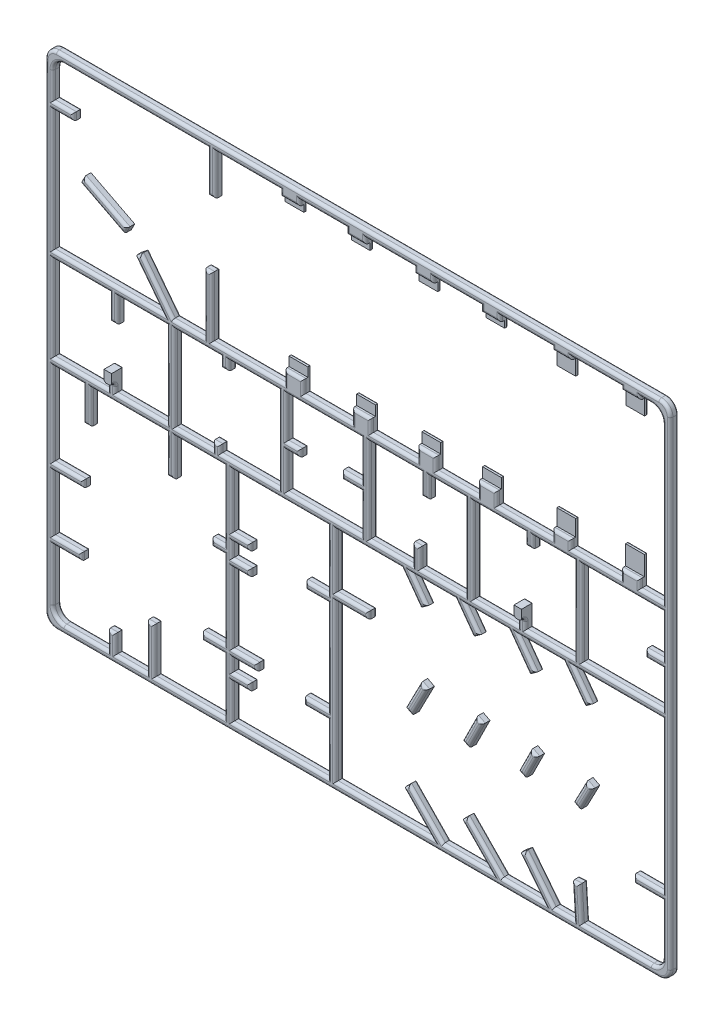
SolidWorks part; units mm, degrees
ref_plane "Front" through (0, 0, 0) normal (0, 0, 1) x (1, 0, 0)
ref_plane "Top" through (0, 0, 0) normal (0, 1, 0) x (1, 0, 0)
ref_plane "Right" through (0, 0, 0) normal (1, 0, 0) x (0, 0, -1)
sketch "Sketch1" plane through (0, 0, 0) normal (0, 0, 1) x (1, 0, 0)
  line L0 (81.8978, -5.241) -> (-82.5193, -5.241)
  line L1 (-34.8288, -65.5735) -> (-34.8288, -5.241)
  line L2 (-82.5193, -65.5735) -> (81.8978, -65.5735)
  line L3 (-82.5193, -65.5735) -> (-82.5193, 65.8623)
  line L4 (-82.5193, 65.8623) -> (81.8978, 65.8623)
  line L5 (81.8978, -65.5735) -> (81.8978, 65.8623)
  line L6 (81.8978, 6.4099) -> (76.3433, 6.4099)
  line L7 (81.8978, 19.4574) -> (-82.5193, 19.4574)
  line L8 (-20.3529, -5.241) -> (-20.3529, 19.4574)
  line L9 (29.3632, -5.241) -> (29.3632, 19.4574)
  line L10 (1.6703, -5.241) -> (1.6703, 19.4574)
  line L11 (-65.8761, -59.6507) -> (-65.8761, -65.5735)
  line L12 (-73.815, -46.4581) -> (-82.5193, -46.4581)
  line L13 (-73.2731, -29.4196) -> (-82.5193, -29.4196)
  line L14 (-72.4385, -15.3166) -> (-72.4385, -5.241)
  line L15 (-41.8719, -48.6764) -> (-34.8288, -48.6764)
  line L16 (-39.2627, -25.7118) -> (-34.8288, -25.7118)
  line L17 (-50.1045, -16.3197) -> (-50.1045, -5.241)
  line L18 (-55.508, -52.42) -> (-55.508, -65.5735)
  line L19 (58.3675, -5.241) -> (58.3675, 19.4574)
  line L20 (-28.9413, -27.8132) -> (-34.8288, -27.8132)
  line L22 (-50.1045, -5.241) -> (-50.1045, 19.4574)
  line L23 (-28.9413, -54.1411) -> (-34.8288, -54.1411)
  line L24 (58.3675, 11.7403) -> (64.5416, 11.7403)
  line L26 (73.1723, -47.1731) -> (81.8978, -47.1731)
  line L27 (-7.2383, -65.5735) -> (-7.2383, -5.241)
  line L28 (-14.2565, -23.1079) -> (-7.2383, -23.1079)
  line L29 (2.5177, -21.8865) -> (-7.2383, -21.8865)
  line L30 (17.225, -12.5359) -> (11.9277, -5.241)
  line L31 (31.253, -12.2024) -> (26.1979, -5.241)
  line L32 (46.253, -13.3582) -> (40.3586, -5.241)
  line L33 (60.9589, -13.3582) -> (55.0137, -5.241)
  line L35 (57.7443, -55.7789) -> (58.3675, -65.5735)
  line L36 (43.6229, -55.7789) -> (51.3233, -65.5735)
  line L37 (28.0749, -55.7789) -> (37.6274, -65.5735)
  line L38 (12.6161, -56.0751) -> (21.8796, -65.5735)
  line L39 (43.3628, -38.0091) -> (46.5638, -31.5955)
  line L40 (57.9117, -38.0091) -> (61.2697, -31.5955)
  line L41 (28.3857, -38.5772) -> (32.0401, -31.2551)
  line L42 (13.1916, -38.5772) -> (17.225, -30.7859)
  line L43 (53.9902, 19.4574) -> (53.9902, 27.0124)
  line L44 (-65.3524, 11.7403) -> (-65.3524, 19.4574)
  line L45 (72.2906, 27.8612) -> (72.2906, 19.4574)
  line L46 (72.3535, 59.8242) -> (72.3535, 65.8623)
  line L47 (53.9902, 59.8242) -> (53.9902, 65.8623)
  line L48 (35.049, 61.4294) -> (35.049, 65.8623)
  line L49 (34.1875, 26.5614) -> (34.1875, 19.4574)
  line L50 (18.0557, 26.5614) -> (18.0557, 19.4574)
  line L51 (0.6748, 26.5614) -> (0.6748, 19.4574)
  line L52 (-17.3279, 26.3151) -> (-17.3279, 19.4574)
  line L53 (-18.3945, 61.4294) -> (-18.3945, 65.8623)
  line L54 (-0.7731, 61.4294) -> (-0.7731, 65.8623)
  line L55 (17.2678, 60.9572) -> (17.2678, 65.8623)
  line L56 (-39.2627, 53.8546) -> (-39.2627, 65.8623)
  line L57 (-40.1658, 36.4171) -> (-40.1658, 19.4574)
  line L58 (-58.8285, 30.7449) -> (-50.1045, 19.4574)
  line L59 (-73.815, 40.5918) -> (-62.1369, 34.5937)
  line L60 (-82.5193, 53.8546) -> (-75.9828, 53.8546)
  line L61 (17.5915, 12.8902) -> (17.5915, 19.4574)
  line L62 (43.3059, 1.1119) -> (43.3059, -5.241)
  line L63 (-37.9496, -2.2) -> (-37.9496, -5.241)
  line L65 (-14.6056, -50.053) -> (-7.2383, -50.053)
  line L66 (28.419, -16.2498) -> (32.3184, -10.6808) construction
  line L67 (-65.8761, -5.241) -> (-65.8761, 0.8715)
  line L68 (-35.7693, 19.4574) -> (-35.7693, 15.7952)
  line L69 (-20.3529, 6.4099) -> (-15.6719, 6.4099)
  line L70 (15.2912, 0.8715) -> (15.2912, -5.241)
  line L71 (45.3566, 15.3416) -> (45.3566, 19.4574)
  line L72 (1.6703, 7.1082) -> (-4.567, 7.1082)
  line L73 (-34.8288, -48.6764) -> (-27.1043, -48.6764)
  line L74 (-34.8288, -21.8865) -> (-28.9413, -21.8865)
  point P122 (-55.508, -52.42)
  point P130 (-39.2627, -25.7118)
  point P131 (-65.3524, 11.7403)
sketch "Sketch3" plane through (0, 0, 0) normal (0, 0, 1) x (1, 0, 0)
  line L0 (1.6703, -5.241) -> (1.6703, 19.4574) construction
  line L1 (29.3632, -5.241) -> (29.3632, 19.4574) construction
  line L2 (-20.3529, -5.241) -> (-20.3529, 19.4574) construction
  line L3 (81.8978, 19.4574) -> (-82.5193, 19.4574) construction
  line L4 (-82.5193, -65.5735) -> (81.8978, -65.5735)
  line L5 (81.8978, -65.5735) -> (81.8978, 65.8623)
  line L6 (81.8978, 65.8623) -> (-82.5193, 65.8623)
  line L7 (-82.5193, 65.8623) -> (-82.5193, -65.5735)
  line L8 (-82.5193, -65.5735) -> (81.8978, -65.5735) construction
  line L9 (81.8978, -65.5735) -> (81.8978, 65.8623) construction
  line L10 (81.8978, 65.8623) -> (-82.5193, 65.8623) construction
  line L11 (-82.5193, 65.8623) -> (-82.5193, -65.5735) construction
  line L12 (-34.8288, -65.5735) -> (-34.8288, -5.241) construction
  line L13 (81.8978, -5.241) -> (-82.5193, -5.241) construction
  line L14 (-55.508, -52.42) -> (-55.508, -65.5735) construction
  line L15 (-50.1045, -16.3197) -> (-50.1045, -5.241) construction
  line L16 (-50.1045, -5.241) -> (-50.1045, 19.4574) construction
  line L17 (-58.8285, 30.7449) -> (-50.1045, 19.4574) construction
  line L18 (-39.2627, -25.7118) -> (-34.8288, -25.7118) construction
  line L19 (-41.8719, -48.6764) -> (-34.8288, -48.6764) construction
  line L20 (-72.4385, -15.3166) -> (-72.4385, -5.241) construction
  line L21 (-73.2731, -29.4196) -> (-82.5193, -29.4196) construction
  line L22 (-73.815, -46.4581) -> (-82.5193, -46.4581) construction
  line L23 (-65.8761, -59.6507) -> (-65.8761, -65.5735) construction
  line L24 (53.9902, 19.4574) -> (53.9902, 27.0124) construction
  line L25 (73.1723, -47.1731) -> (81.8978, -47.1731) construction
  line L27 (58.3675, 11.7403) -> (64.5416, 11.7403) construction
  line L28 (-28.9413, -54.1411) -> (-34.8288, -54.1411) construction
  line L29 (44.3566, 15.3416) -> (46.3566, 15.3416)
  line L30 (-28.9413, -27.8132) -> (-34.8288, -27.8132) construction
  line L31 (58.3675, -5.241) -> (58.3675, 19.4574) construction
  line L32 (46.3566, 15.3416) -> (46.3566, 19.4574)
  line L33 (60.9589, -13.3582) -> (55.0137, -5.241) construction
  line L34 (46.253, -13.3582) -> (40.3586, -5.241) construction
  line L35 (31.253, -12.2024) -> (26.1979, -5.241) construction
  line L36 (17.225, -12.5359) -> (11.9277, -5.241) construction
  line L37 (2.5177, -21.8865) -> (-7.2383, -21.8865) construction
  line L38 (-14.2565, -23.1079) -> (-7.2383, -23.1079) construction
  line L39 (-7.2383, -65.5735) -> (-7.2383, -5.241) construction
  line L40 (13.1916, -38.5772) -> (17.225, -30.7859) construction
  line L41 (28.3857, -38.5772) -> (32.0401, -31.2551) construction
  line L42 (57.9117, -38.0091) -> (61.2697, -31.5955) construction
  line L43 (43.3628, -38.0091) -> (46.5638, -31.5955) construction
  line L44 (12.6161, -56.0751) -> (21.8796, -65.5735) construction
  line L45 (28.0749, -55.7789) -> (37.6274, -65.5735) construction
  line L46 (43.6229, -55.7789) -> (51.3233, -65.5735) construction
  line L47 (57.7443, -55.7789) -> (58.3675, -65.5735) construction
  line L48 (18.0557, 26.5614) -> (18.0557, 19.4574) construction
  line L49 (34.1875, 26.5614) -> (34.1875, 19.4574) construction
  line L50 (35.049, 61.4294) -> (35.049, 65.8623) construction
  line L51 (53.9902, 59.8242) -> (53.9902, 65.8623) construction
  line L52 (72.3535, 59.8242) -> (72.3535, 65.8623) construction
  line L53 (72.2906, 27.8612) -> (72.2906, 19.4574) construction
  line L54 (-65.3524, 11.7403) -> (-65.3524, 19.4574) construction
  line L55 (81.8978, 6.4099) -> (76.3433, 6.4099) construction
  line L56 (-40.1658, 36.4171) -> (-40.1658, 19.4574) construction
  line L57 (-39.2627, 53.8546) -> (-39.2627, 65.8623) construction
  line L58 (17.2678, 60.9572) -> (17.2678, 65.8623) construction
  line L59 (-0.7731, 61.4294) -> (-0.7731, 65.8623) construction
  line L60 (-18.3945, 61.4294) -> (-18.3945, 65.8623) construction
  line L61 (-17.3279, 26.3151) -> (-17.3279, 19.4574) construction
  line L62 (0.6748, 26.5614) -> (0.6748, 19.4574) construction
  line L63 (-14.6056, -50.053) -> (-7.2383, -50.053) construction
  line L64 (46.3566, 15.3416) -> (46.3566, 18.4574)
  line L65 (-37.9496, -2.2) -> (-37.9496, -5.241) construction
  line L66 (43.3059, 1.1119) -> (43.3059, -5.241) construction
  line L67 (17.5915, 12.8902) -> (17.5915, 19.4574) construction
  line L68 (-82.5193, 53.8546) -> (-75.9828, 53.8546) construction
  line L69 (-73.815, 40.5918) -> (-62.1369, 34.5937) construction
  line L70 (1.6703, -5.241) -> (1.6703, 19.4574) construction
  line L71 (29.3632, -5.241) -> (29.3632, 19.4574) construction
  line L72 (-20.3529, -5.241) -> (-20.3529, 19.4574) construction
  line L73 (81.8978, 19.4574) -> (-82.5193, 19.4574) construction
  line L74 (-34.8288, -65.5735) -> (-34.8288, -5.241) construction
  line L75 (81.8978, -5.241) -> (-82.5193, -5.241) construction
  line L76 (-55.508, -52.42) -> (-55.508, -65.5735) construction
  line L77 (-50.1045, -16.3197) -> (-50.1045, -5.241) construction
  line L78 (-50.1045, -5.241) -> (-50.1045, 19.4574) construction
  line L79 (-58.8285, 30.7449) -> (-50.1045, 19.4574) construction
  line L80 (-39.2627, -25.7118) -> (-34.8288, -25.7118) construction
  line L81 (-41.8719, -48.6764) -> (-34.8288, -48.6764) construction
  line L82 (-72.4385, -15.3166) -> (-72.4385, -5.241) construction
  line L83 (-73.2731, -29.4196) -> (-82.5193, -29.4196) construction
  line L84 (-73.815, -46.4581) -> (-82.5193, -46.4581) construction
  line L85 (-65.8761, -59.6507) -> (-65.8761, -65.5735) construction
  line L86 (53.9902, 19.4574) -> (53.9902, 27.0124) construction
  line L87 (73.1723, -47.1731) -> (81.8978, -47.1731) construction
  line L88 (44.3566, 15.3416) -> (44.3566, 19.4574)
  line L89 (58.3675, 11.7403) -> (64.5416, 11.7403) construction
  line L90 (-28.9413, -54.1411) -> (-34.8288, -54.1411) construction
  line L91 (44.3566, 15.3416) -> (44.3566, 18.4574)
  line L92 (-28.9413, -27.8132) -> (-34.8288, -27.8132) construction
  line L93 (58.3675, -5.241) -> (58.3675, 19.4574) construction
  line L94 (-36.7693, 15.7952) -> (-34.7693, 15.7952)
  line L95 (60.9589, -13.3582) -> (55.0137, -5.241) construction
  line L96 (46.253, -13.3582) -> (40.3586, -5.241) construction
  line L97 (31.253, -12.2024) -> (26.1979, -5.241) construction
  line L98 (17.225, -12.5359) -> (11.9277, -5.241) construction
  line L99 (2.5177, -21.8865) -> (-7.2383, -21.8865) construction
  line L100 (-14.2565, -23.1079) -> (-7.2383, -23.1079) construction
  line L101 (-7.2383, -65.5735) -> (-7.2383, -5.241) construction
  line L102 (13.1916, -38.5772) -> (17.225, -30.7859) construction
  line L103 (28.3857, -38.5772) -> (32.0401, -31.2551) construction
  line L104 (57.9117, -38.0091) -> (61.2697, -31.5955) construction
  line L105 (43.3628, -38.0091) -> (46.5638, -31.5955) construction
  line L106 (12.6161, -56.0751) -> (21.8796, -65.5735) construction
  line L107 (28.0749, -55.7789) -> (37.6274, -65.5735) construction
  line L108 (43.6229, -55.7789) -> (51.3233, -65.5735) construction
  line L109 (57.7443, -55.7789) -> (58.3675, -65.5735) construction
  line L110 (18.0557, 26.5614) -> (18.0557, 19.4574) construction
  line L111 (34.1875, 26.5614) -> (34.1875, 19.4574) construction
  line L112 (35.049, 61.4294) -> (35.049, 65.8623) construction
  line L113 (53.9902, 59.8242) -> (53.9902, 65.8623) construction
  line L114 (72.3535, 59.8242) -> (72.3535, 65.8623) construction
  line L115 (72.2906, 27.8612) -> (72.2906, 19.4574) construction
  line L116 (-65.3524, 11.7403) -> (-65.3524, 19.4574) construction
  line L117 (81.8978, 6.4099) -> (76.3433, 6.4099) construction
  line L118 (-40.1658, 36.4171) -> (-40.1658, 19.4574) construction
  line L119 (-39.2627, 53.8546) -> (-39.2627, 65.8623) construction
  line L120 (17.2678, 60.9572) -> (17.2678, 65.8623) construction
  line L121 (-0.7731, 61.4294) -> (-0.7731, 65.8623) construction
  line L122 (-18.3945, 61.4294) -> (-18.3945, 65.8623) construction
  line L123 (-17.3279, 26.3151) -> (-17.3279, 19.4574) construction
  line L124 (0.6748, 26.5614) -> (0.6748, 19.4574) construction
  line L125 (-14.6056, -50.053) -> (-7.2383, -50.053) construction
  line L126 (44.3566, 18.4574) -> (30.3632, 18.4574)
  line L127 (-37.9496, -2.2) -> (-37.9496, -5.241) construction
  line L128 (43.3059, 1.1119) -> (43.3059, -5.241) construction
  line L129 (17.5915, 12.8902) -> (17.5915, 19.4574) construction
  line L130 (-82.5193, 53.8546) -> (-75.9828, 53.8546) construction
  line L131 (-73.815, 40.5918) -> (-62.1369, 34.5937) construction
  line L132 (-80.5193, -66.5735) -> (79.8978, -66.5735)
  line L133 (82.8978, -63.5735) -> (82.8978, 63.8623)
  line L134 (79.8978, 66.8623) -> (-80.5193, 66.8623)
  line L135 (-83.5193, 63.8623) -> (-83.5193, -63.5735)
  line L136 (2.6703, -4.241) -> (2.6703, 18.4574)
  line L137 (30.3632, -4.241) -> (30.3632, 18.4574)
  line L138 (-19.3529, -4.241) -> (-19.3529, 5.4099)
  line L139 (80.8978, 20.4574) -> (74.7906, 20.4574)
  line L140 (-33.8288, -64.5735) -> (-33.8288, -55.1411)
  line L141 (80.8978, -4.241) -> (59.3675, -4.241)
  line L142 (-56.508, -52.42) -> (-56.508, -64.5735)
  line L143 (-49.1045, -16.3197) -> (-49.1045, -6.241)
  line L144 (-49.1045, -4.241) -> (-49.1045, 18.4574)
  line L145 (-58.0373, 31.3564) -> (-49.6135, 20.4574)
  line L146 (-39.2627, -26.7118) -> (-35.8288, -26.7118)
  line L147 (-41.8719, -49.6764) -> (-35.8288, -49.6764)
  line L148 (-71.4385, -15.3166) -> (-71.4385, -6.241)
  line L149 (-73.2731, -28.4196) -> (-81.5193, -28.4196)
  line L150 (-73.815, -45.4581) -> (-81.5193, -45.4581)
  line L151 (-66.8761, -59.6507) -> (-66.8761, -64.5735)
  line L152 (56.4902, 20.4574) -> (56.4902, 27.0124)
  line L153 (73.1723, -48.1731) -> (80.8978, -48.1731)
  line L155 (59.3675, 10.7403) -> (64.5416, 10.7403)
  line L156 (-28.9413, -53.1411) -> (-33.8288, -53.1411)
  line L158 (-28.9413, -26.8132) -> (-33.8288, -26.8132)
  line L159 (59.3675, -4.241) -> (59.3675, 10.7403)
  line L161 (61.7657, -12.7673) -> (56.9857, -6.241)
  line L162 (47.0622, -12.7706) -> (42.3207, -6.241)
  line L163 (32.0622, -11.6148) -> (28.1599, -6.241)
  line L164 (18.0342, -11.9484) -> (13.8897, -6.241)
  line L165 (2.5177, -20.8865) -> (-6.2383, -20.8865)
  line L166 (-14.2565, -24.1079) -> (-8.2383, -24.1079)
  line L167 (-6.2383, -64.5735) -> (-6.2383, -22.8865)
  line L168 (14.0797, -39.0369) -> (18.1131, -31.2457)
  line L169 (29.2805, -39.0237) -> (32.9349, -31.7017)
  line L170 (58.7976, -38.473) -> (62.1556, -32.0593)
  line L171 (44.2575, -38.4557) -> (47.4585, -32.042)
  line L172 (11.9002, -56.7733) -> (19.5075, -64.5735)
  line L173 (27.359, -56.4771) -> (35.2553, -64.5735)
  line L174 (42.8368, -56.3969) -> (49.265, -64.5735)
  line L175 (56.7464, -55.8424) -> (57.3019, -64.5735)
  line L176 (15.5557, 26.5614) -> (15.5557, 20.4574)
  line L177 (31.6875, 26.5614) -> (31.6875, 20.4574)
  line L178 (37.549, 61.4294) -> (37.549, 64.8623)
  line L179 (56.4902, 59.8242) -> (56.4902, 64.8623)
  line L180 (74.8535, 59.8242) -> (74.8535, 64.8623)
  line L181 (69.7906, 27.8612) -> (69.7906, 20.4574)
  line L182 (-64.3524, 11.7403) -> (-64.3524, 18.4574)
  line L183 (80.8978, 7.4099) -> (76.3433, 7.4099)
  line L184 (-41.1658, 36.4171) -> (-41.1658, 20.4574)
  line L185 (-38.2627, 53.8546) -> (-38.2627, 64.8623)
  line L186 (19.7678, 60.9572) -> (19.7678, 64.8623)
  line L187 (1.7269, 61.4294) -> (1.7269, 64.8623)
  line L188 (-15.8945, 61.4294) -> (-15.8945, 64.8623)
  line L189 (-19.8279, 26.3151) -> (-19.8279, 20.4574)
  line L190 (-1.8252, 26.5614) -> (-1.8252, 20.4574)
  line L191 (-14.6056, -51.053) -> (-8.2383, -51.053)
  line L193 (-38.9496, -2.2) -> (-38.9496, -4.241)
  line L194 (42.3059, 1.1119) -> (42.3059, -4.241)
  line L195 (18.5915, 12.8902) -> (18.5915, 18.4574)
  line L196 (-81.5193, 52.8546) -> (-75.9828, 52.8546)
  line L197 (-74.2719, 39.7022) -> (-62.5938, 33.7042)
  line L198 (-78.5193, -64.5735) -> (-66.8761, -64.5735)
  line L199 (80.8978, -61.5735) -> (80.8978, -48.1731)
  line L200 (77.8978, 64.8623) -> (74.8535, 64.8623)
  line L201 (-81.5193, 61.8623) -> (-81.5193, 54.8546)
  line L202 (0.6703, -4.241) -> (0.6703, 6.1082)
  line L203 (28.3632, -4.241) -> (28.3632, 18.4574)
  line L204 (-21.3529, -4.241) -> (-21.3529, 18.4574)
  line L205 (80.8978, 18.4574) -> (59.3675, 18.4574)
  line L206 (-35.8288, -64.5735) -> (-35.8288, -49.6764)
  line L207 (80.8978, -6.241) -> (56.9857, -6.241)
  line L208 (-54.508, -52.42) -> (-54.508, -64.5735)
  line L209 (-51.1045, -16.3197) -> (-51.1045, -6.241)
  line L210 (-51.1045, -4.241) -> (-51.1045, 18.4574)
  line L211 (-59.6197, 30.1333) -> (-52.1413, 20.4574)
  line L212 (-39.2627, -24.7118) -> (-35.8288, -24.7118)
  line L213 (-41.8719, -47.6764) -> (-35.8288, -47.6764)
  line L214 (-73.4385, -15.3166) -> (-73.4385, -6.241)
  line L215 (-73.2731, -30.4196) -> (-81.5193, -30.4196)
  line L216 (-73.815, -47.4581) -> (-81.5193, -47.4581)
  line L217 (-64.8761, -59.6507) -> (-64.8761, -64.5735)
  line L218 (51.4902, 20.4574) -> (51.4902, 27.0124)
  line L219 (73.1723, -46.1731) -> (80.8978, -46.1731)
  line L221 (59.3675, 7.9351) -> (64.5416, 7.9351)
  line L222 (-28.9413, -55.1411) -> (-33.8288, -55.1411)
  line L224 (-28.9413, -28.8132) -> (-33.8288, -28.8132)
  line L225 (57.3675, -4.241) -> (57.3675, 18.4574)
  line L227 (60.1522, -13.949) -> (54.5066, -6.241)
  line L228 (45.4439, -13.9457) -> (39.849, -6.241)
  line L229 (30.4438, -12.79) -> (25.6882, -6.241)
  line L230 (16.4159, -13.1235) -> (11.418, -6.241)
  line L231 (2.5177, -22.8865) -> (-6.2383, -22.8865)
  line L232 (-14.2565, -22.1079) -> (-8.2383, -22.1079)
  line L233 (-8.2383, -64.5735) -> (-8.2383, -51.053)
  line L234 (12.3035, -38.1174) -> (16.337, -30.3262)
  line L235 (27.491, -38.1306) -> (31.1454, -30.8085)
  line L236 (57.0258, -37.5453) -> (60.3838, -31.1316)
  line L237 (42.468, -37.5626) -> (45.669, -31.1489)
  line L238 (13.332, -55.3769) -> (22.3011, -64.5735)
  line L239 (28.7909, -55.0807) -> (38.0489, -64.5735)
  line L240 (44.4091, -55.1608) -> (51.8091, -64.5735)
  line L241 (58.7423, -55.7154) -> (59.3059, -64.5735)
  line L242 (20.5557, 26.5614) -> (20.5557, 20.4574)
  line L243 (36.6875, 26.5614) -> (36.6875, 20.4574)
  line L244 (32.549, 61.4294) -> (32.549, 64.8623)
  line L245 (51.4902, 59.8242) -> (51.4902, 64.8623)
  line L246 (69.8535, 59.8242) -> (69.8535, 64.8623)
  line L247 (74.7906, 27.8612) -> (74.7906, 20.4574)
  line L248 (-66.3524, 11.7403) -> (-66.3524, 18.4574)
  line L249 (80.8978, 5.4099) -> (76.3433, 5.4099)
  line L250 (-39.1658, 36.4171) -> (-39.1658, 20.4574)
  line L251 (-40.2627, 53.8546) -> (-40.2627, 64.8623)
  line L252 (14.7678, 60.9572) -> (14.7678, 64.8623)
  line L253 (-3.2731, 61.4294) -> (-3.2731, 64.8623)
  line L254 (-20.8945, 61.4294) -> (-20.8945, 64.8623)
  line L255 (-14.8279, 26.3151) -> (-14.8279, 20.4574)
  line L256 (3.1748, 26.5614) -> (3.1748, 20.4574)
  line L257 (-14.6056, -49.053) -> (-8.2383, -49.053)
  line L259 (-36.9496, -2.2) -> (-36.9496, -4.241)
  line L260 (44.3059, 1.1119) -> (44.3059, -4.241)
  line L261 (16.5915, 12.8902) -> (16.5915, 18.4574)
  line L262 (-81.5193, 54.8546) -> (-75.9828, 54.8546)
  line L263 (-73.3581, 41.4813) -> (-61.6801, 35.4832)
  line L264 (-59.6197, 30.1333) -> (-58.0373, 31.3564)
  line L265 (-41.1658, 36.4171) -> (-39.1658, 36.4171)
  line L266 (-19.8279, 26.3151) -> (-14.8279, 26.3151)
  line L267 (-1.8252, 26.5614) -> (3.1748, 26.5614)
  line L268 (15.5557, 26.5614) -> (20.5557, 26.5614)
  line L269 (31.6875, 26.5614) -> (36.6875, 26.5614)
  line L270 (51.4902, 27.0124) -> (56.4902, 27.0124)
  line L271 (76.3433, 5.4099) -> (76.3433, 7.4099)
  line L272 (64.5416, 7.9351) -> (64.5416, 10.7403)
  line L273 (69.7906, 27.8612) -> (74.7906, 27.8612)
  line L274 (74.8535, 59.8242) -> (69.8535, 59.8242)
  line L275 (51.4902, 59.8242) -> (56.4902, 59.8242)
  line L276 (14.7678, 60.9572) -> (19.7678, 60.9572)
  line L277 (32.549, 61.4294) -> (37.549, 61.4294)
  line L278 (-3.2731, 61.4294) -> (1.7269, 61.4294)
  line L279 (-20.8945, 61.4294) -> (-15.8945, 61.4294)
  line L280 (-62.5938, 33.7042) -> (-61.6801, 35.4832)
  line L281 (-73.3581, 41.4813) -> (-74.2719, 39.7022)
  line L282 (-75.9828, 52.8546) -> (-75.9828, 54.8546)
  line L283 (-40.2627, 53.8546) -> (-38.2627, 53.8546)
  line L284 (-66.3524, 11.7403) -> (-64.3524, 11.7403)
  line L285 (-73.4385, -15.3166) -> (-71.4385, -15.3166)
  line L286 (-51.1045, -16.3197) -> (-49.1045, -16.3197)
  line L287 (-39.2627, -24.7118) -> (-39.2627, -26.7118)
  line L288 (-14.2565, -22.1079) -> (-14.2565, -24.1079)
  line L290 (-28.9413, -26.8132) -> (-28.9413, -28.8132)
  line L291 (-73.2731, -28.4196) -> (-73.2731, -30.4196)
  line L293 (2.5177, -22.8865) -> (2.5177, -20.8865)
  line L294 (16.4159, -13.1235) -> (18.0342, -11.9484)
  line L295 (30.4438, -12.79) -> (32.0622, -11.6148)
  line L296 (45.4439, -13.9457) -> (47.0622, -12.7706)
  line L297 (60.1522, -13.949) -> (61.7657, -12.7673)
  line L299 (58.7976, -38.473) -> (57.0258, -37.5453)
  line L300 (45.669, -31.1489) -> (47.4585, -32.042)
  line L301 (60.3838, -31.1316) -> (62.1556, -32.0593)
  line L302 (42.468, -37.5626) -> (44.2575, -38.4557)
  line L303 (27.491, -38.1306) -> (29.2805, -39.0237)
  line L304 (16.337, -30.3262) -> (18.1131, -31.2457)
  line L305 (31.1454, -30.8085) -> (32.9349, -31.7017)
  line L306 (12.3035, -38.1174) -> (14.0797, -39.0369)
  line L307 (73.1723, -46.1731) -> (73.1723, -48.1731)
  line L309 (58.7423, -55.7154) -> (56.7464, -55.8424)
  line L310 (44.4091, -55.1608) -> (42.8368, -56.3969)
  line L311 (28.7909, -55.0807) -> (27.359, -56.4771)
  line L312 (11.9002, -56.7733) -> (13.332, -55.3769)
  line L313 (-28.9413, -53.1411) -> (-28.9413, -55.1411)
  line L314 (-14.6056, -49.053) -> (-14.6056, -51.053)
  line L315 (-41.8719, -47.6764) -> (-41.8719, -49.6764)
  line L316 (-56.508, -52.42) -> (-54.508, -52.42)
  line L317 (16.5915, 12.8902) -> (18.5915, 12.8902)
  line L327 (80.8978, 20.4574) -> (80.8978, 61.8623)
  line L331 (69.7906, 20.4574) -> (56.4902, 20.4574)
  line L333 (57.3675, 18.4574) -> (46.3566, 18.4574)
  line L336 (51.4902, 20.4574) -> (36.6875, 20.4574)
  line L339 (31.6875, 20.4574) -> (20.5557, 20.4574)
  line L342 (28.3632, 18.4574) -> (18.5915, 18.4574)
  line L345 (16.5915, 18.4574) -> (2.6703, 18.4574)
  line L347 (15.5557, 20.4574) -> (3.1748, 20.4574)
  line L351 (0.6703, 18.4574) -> (-19.3529, 18.4574)
  line L354 (-1.8252, 20.4574) -> (-14.8279, 20.4574)
  line L357 (-19.8279, 20.4574) -> (-39.1658, 20.4574)
  line L360 (-21.3529, 18.4574) -> (-34.7693, 18.4574)
  line L363 (-41.1658, 20.4574) -> (-49.6135, 20.4574)
  line L365 (-51.1045, -4.241) -> (-64.8761, -4.241)
  line L367 (-51.1045, 18.4574) -> (-64.3524, 18.4574)
  line L371 (-52.1413, 20.4574) -> (-81.5193, 20.4574)
  line L373 (-66.3524, 18.4574) -> (-81.5193, 18.4574)
  line L375 (-81.5193, 18.4574) -> (-81.5193, -4.241)
  line L377 (-81.5193, 52.8546) -> (-81.5193, 20.4574)
  line L380 (-40.2627, 64.8623) -> (-78.5193, 64.8623)
  line L383 (-20.8945, 64.8623) -> (-38.2627, 64.8623)
  line L386 (14.7678, 64.8623) -> (1.7269, 64.8623)
  line L389 (-3.2731, 64.8623) -> (-15.8945, 64.8623)
  line L392 (32.549, 64.8623) -> (19.7678, 64.8623)
  line L395 (69.8535, 64.8623) -> (56.4902, 64.8623)
  line L398 (51.4902, 64.8623) -> (37.549, 64.8623)
  line L400 (-81.5193, -6.241) -> (-81.5193, -28.4196)
  line L404 (-73.4385, -6.241) -> (-81.5193, -6.241)
  line L407 (-51.1045, -6.241) -> (-71.4385, -6.241)
  line L410 (-38.9496, -4.241) -> (-49.1045, -4.241)
  line L413 (-35.8288, -6.241) -> (-49.1045, -6.241)
  line L415 (-28.9413, -20.8865) -> (-28.9413, -22.8865)
  line L417 (-34.8288, -22.8865) -> (-28.9413, -22.8865)
  line L421 (-8.2383, -6.241) -> (-33.8288, -6.241)
  line L422 (-6.2383, -20.8865) -> (-6.2383, -6.241)
  line L424 (-35.8288, -24.7118) -> (-35.8288, -6.241)
  line L427 (-8.2383, -22.1079) -> (-8.2383, -6.241)
  line L430 (28.3632, -4.241) -> (16.2912, -4.241)
  line L432 (25.6882, -6.241) -> (13.8897, -6.241)
  line L434 (11.418, -6.241) -> (-6.2383, -6.241)
  line L436 (57.3675, -4.241) -> (44.3059, -4.241)
  line L439 (39.849, -6.241) -> (28.1599, -6.241)
  line L442 (54.5066, -6.241) -> (42.3207, -6.241)
  line L445 (42.3059, -4.241) -> (30.3632, -4.241)
  line L448 (59.3675, 7.9351) -> (59.3675, 18.4574)
  line L451 (80.8978, 7.4099) -> (80.8978, 18.4574)
  line L453 (80.8978, -4.241) -> (80.8978, 5.4099)
  line L454 (-36.7693, 19.4574) -> (-36.7693, 15.7952)
  line L456 (-36.7693, 18.4574) -> (-36.7693, 15.7952)
  line L458 (80.8978, -46.1731) -> (80.8978, -6.241)
  line L461 (-34.7693, 19.4574) -> (-34.7693, 15.7952)
  line L462 (59.3059, -64.5735) -> (77.8978, -64.5735)
  line L463 (-34.7693, 18.4574) -> (-34.7693, 15.7952)
  line L466 (-6.2383, -64.5735) -> (19.5075, -64.5735)
  line L468 (51.8091, -64.5735) -> (57.3019, -64.5735)
  line L471 (22.3011, -64.5735) -> (35.2553, -64.5735)
  line L474 (38.0489, -64.5735) -> (49.265, -64.5735)
  line L476 (-33.8288, -64.5735) -> (-8.2383, -64.5735)
  line L478 (-54.508, -64.5735) -> (-35.8288, -64.5735)
  line L481 (-64.8761, -64.5735) -> (-56.508, -64.5735)
  line L484 (-81.5193, -47.4581) -> (-81.5193, -61.5735)
  line L487 (-81.5193, -30.4196) -> (-81.5193, -45.4581)
  line L489 (-27.1043, -47.6764) -> (-27.1043, -49.6764)
  line L490 (-8.2383, -49.053) -> (-8.2383, -24.1079)
  line L491 (-34.8288, -49.6764) -> (-27.1043, -49.6764)
  line L496 (-33.8288, -53.1411) -> (-33.8288, -49.6764)
  line L499 (-35.8288, -47.6764) -> (-35.8288, -26.7118)
  line L501 (-66.8761, -59.6507) -> (-64.8761, -59.6507)
  line L502 (-73.815, -45.4581) -> (-73.815, -47.4581)
  line L503 (-38.9496, -2.2) -> (-36.9496, -2.2)
  line L504 (0.6703, -4.241) -> (-19.3529, -4.241)
  line L505 (42.3059, 1.1119) -> (44.3059, 1.1119)
  line L506 (-21.3529, -4.241) -> (-36.9496, -4.241)
  line L508 (-33.8288, -26.8132) -> (-33.8288, -22.8865)
  line L511 (-64.8761, 0.8715) -> (-66.8761, 0.8715)
  line L512 (-64.8761, -5.241) -> (-64.8761, 0.8715)
  line L513 (-64.8761, -4.241) -> (-64.8761, 0.8715)
  line L514 (-66.8761, -5.241) -> (-66.8761, 0.8715)
  line L515 (-66.8761, -4.241) -> (-66.8761, 0.8715)
  line L516 (-66.8761, -4.241) -> (-81.5193, -4.241)
  line L517 (-36.7693, 18.4574) -> (-49.1045, 18.4574)
  line L523 (-20.3529, 5.4099) -> (-15.6719, 5.4099)
  line L524 (-19.3529, 5.4099) -> (-15.6719, 5.4099)
  line L525 (-20.3529, 7.4099) -> (-15.6719, 7.4099)
  line L526 (-19.3529, 7.4099) -> (-15.6719, 7.4099)
  line L527 (-4.567, 6.1082) -> (-4.567, 8.1082)
  line L528 (1.6703, 8.1082) -> (-4.567, 8.1082)
  line L529 (0.6703, 8.1082) -> (-4.567, 8.1082)
  line L530 (1.6703, 6.1082) -> (-4.567, 6.1082)
  line L531 (0.6703, 6.1082) -> (-4.567, 6.1082)
  line L532 (-15.6719, 5.4099) -> (-15.6719, 7.4099)
  line L533 (-19.3529, 7.4099) -> (-19.3529, 18.4574)
  line L534 (0.6703, 8.1082) -> (0.6703, 18.4574)
  line L536 (16.2912, 0.8715) -> (14.2912, 0.8715)
  line L537 (14.2912, 0.8715) -> (14.2912, -5.241)
  line L538 (14.2912, 0.8715) -> (14.2912, -4.241)
  line L539 (16.2912, 0.8715) -> (16.2912, -5.241)
  line L540 (16.2912, 0.8715) -> (16.2912, -4.241)
  line L541 (14.2912, -4.241) -> (2.6703, -4.241)
  line L542 (-33.8288, -49.6764) -> (-27.1043, -49.6764)
  line L543 (-34.8288, -47.6764) -> (-27.1043, -47.6764)
  line L544 (-33.8288, -47.6764) -> (-27.1043, -47.6764)
  line L545 (-33.8288, -47.6764) -> (-33.8288, -28.8132)
  line L546 (-33.8288, -22.8865) -> (-28.9413, -22.8865)
  line L547 (-34.8288, -20.8865) -> (-28.9413, -20.8865)
  line L548 (-33.8288, -20.8865) -> (-28.9413, -20.8865)
  line L550 (-33.8288, -20.8865) -> (-33.8288, -6.241)
  arc A0 (-80.5193, 66.8623) -> (-83.5193, 63.8623) centre (-80.5193, 63.8623) ccw
  arc A1 (-78.5193, 64.8623) -> (-81.5193, 61.8623) centre (-78.5193, 61.8623) ccw
  arc A2 (-80.5193, -66.5735) -> (-83.5193, -63.5735) centre (-80.5193, -63.5735) cw
  arc A3 (-78.5193, -64.5735) -> (-81.5193, -61.5735) centre (-78.5193, -61.5735) cw
  arc A4 (79.8978, -66.5735) -> (82.8978, -63.5735) centre (79.8978, -63.5735) ccw
  arc A5 (82.8978, 63.8623) -> (79.8978, 66.8623) centre (79.8978, 63.8623) ccw
  arc A6 (80.8978, 61.8623) -> (77.8978, 64.8623) centre (77.8978, 61.8623) ccw
  arc A7 (80.8978, -61.5735) -> (77.8978, -64.5735) centre (77.8978, -61.5735) cw
  point P131 (-33.8288, -51.4087)
  point P132 (-38.9496, -3.2205)
  point P133 (72.2906, 27.8612)
  point P134 (53.9902, 27.0124)
  point P135 (34.1875, 26.5614)
  point P136 (20.2946, 26.6853)
  point P137 (-13.8432, 26.3558)
  point P138 (3.9799, 26.7284)
  point P139 (21.8031, 27.0389)
  point P140 (18.0557, 26.5614)
  point P141 (0.6748, 26.5614)
  point P143 (-17.3279, 26.3151)
  point P145 (0, 0)
  point P146 (-65.3524, 11.7403)
  point P149 (-18.3945, 61.4294)
  point P151 (-0.7731, 61.4294)
  point P153 (17.2678, 60.9572)
  point P155 (35.049, 61.4294)
  point P157 (53.9902, 59.8242)
  point P159 (72.3535, 59.8242)
  dimension "D4" = 3
  dimension "D5" = 3
  dimension "D6" = 1
  dimension "D8" = 1
  dimension "D10" = 1
  dimension "D14" = 1
  dimension "D16" = 1
  dimension "D18" = 1
  dimension "D20" = 1
  dimension "D2" = 1
  dimension "D3" = 1
  dimension "D21" = 1
  dimension "D22" = 1
  dimension "D23" = 1
  dimension "D24" = 1
  dimension "D25" = 1
  dimension "D26" = 1
  dimension "D27" = 1
  dimension "D30" = 1
  dimension "D31" = 1
  dimension "D32" = 1
  dimension "D33" = 1
  dimension "D34" = 1
  dimension "D35" = 1
  dimension "D36" = 1
  dimension "D37" = 1
  dimension "D38" = 1
  dimension "D39" = 1
  dimension "D40" = 1
  dimension "D41" = 1
  dimension "D42" = 1
  dimension "D43" = 1
  dimension "D44" = 1
  dimension "D45" = 1
  dimension "D46" = 1
  dimension "D47" = 1
  dimension "D48" = 1
  dimension "D49" = 1
  dimension "D50" = 1
  dimension "D51" = 1
  dimension "D52" = 1
  dimension "D53" = 1
  dimension "D54" = 1
  dimension "D55" = 1
  dimension "D56" = 1
  dimension "D57" = 1
  dimension "D58" = 2
  dimension "D59" = 1
  dimension "D60" = 1
  dimension "D61" = 1
  dimension "D62" = 1
  dimension "D63" = 1
  dimension "D64" = 1
  dimension "D65" = 1
  dimension "D66" = 1
  dimension "D67" = 1
  dimension "D68" = 1
  dimension "D69" = 1
  dimension "D70" = 1
  dimension "D71" = 5
  dimension "D72" = 1
  dimension "D73" = 1
  dimension "D74" = 1
  dimension "D1" = 0
  dimension "D7" = 1
  dimension "D9" = 1
  dimension "D11" = 1
  dimension "D12" = 1
  dimension "D13" = 1
  dimension "D15" = 1
  dimension "D17" = 1
  dimension "D19" = 1
  dimension "D28" = 1
  dimension "D29" = 1
extrude "Boss-Extrude1" add sketch "Sketch3" along normal blind 2 contours L133 A5 L134 A0 L135 A2 L132 A4 L505 L194 L445 L137 L333 L225 L436 L260 L453 L141 L159 L155 L272 L221 L448 L205 L451 L183 L271 L249 L375 L373 L248 L284 L182 L367 L210 L365 L203 L430 L136 L345 L261 L317 L195 L342 L202 L504 | L263 L281 L197 L280 | L301 L236 L299 L170 | L237 L302 L171 L300 | L305 L235 L303 L169 | L234 L306 L168 L304
sketch "Sketch4" plane through (0, 0, 0) normal (0, 0, 1) x (1, 0, 0)
  line L0 (44.1415, 63.2557) -> (44.1415, 63.947)
  line L1 (-26.7077, 63.2557) -> (44.1415, 63.2557)
  line L2 (-26.7077, 63.2557) -> (-26.7077, 23.9146)
  line L3 (-26.7077, 23.9146) -> (44.1415, 23.9146)
  line L5 (79.1511, 22.733) -> (44.1415, 22.733)
  line L6 (79.1511, 22.733) -> (79.1511, 63.947)
  line L7 (79.1511, 63.947) -> (44.1415, 63.947)
  line L8 (44.1415, 22.733) -> (44.1415, 23.9146)
extrude "Cut-Extrude1" cut sketch "Sketch4" along normal blind 10 from offset 0.75
sketch "Sketch5" plane through (0, 0, 2) normal (0, 0, 1) x (1, 0, 0)
  line L0 (-64.8761, -4.241) -> (-64.8761, 0.8715) construction
  line L1 (-64.8761, -2.0692) -> (-66.8761, -2.0692)
  line L2 (-64.8761, -2.0692) -> (-64.8761, 0.8715)
  line L3 (-64.8761, 0.8715) -> (-66.8761, 0.8715)
  line L4 (-66.8761, -2.0692) -> (-66.8761, 0.8715)
  line L5 (-66.8761, -4.241) -> (-66.8761, 0.8715) construction
  line L6 (42.3059, 1.1119) -> (42.3059, -4.241) construction
  line L7 (42.3059, -1.6848) -> (44.3059, -1.6848)
  line L8 (42.3059, -1.6848) -> (42.3059, 1.1119)
  line L9 (42.3059, 1.1119) -> (44.3059, 1.1119)
  line L10 (44.3059, -1.6848) -> (44.3059, 1.1119)
  line L11 (44.3059, 1.1119) -> (44.3059, -4.241) construction
extrude "Boss-Extrude2" add sketch "Sketch5" along normal blind 1
fillet "Fillet1" radius 0.75 52 edges at (77.0351, -48.1731, 2) (59.3757, -9.5041, 2) (60.9589, -13.3582, 2) (57.3294, -10.095, 2) (44.6914, -9.5058, 2) (30.111, -8.9279, 2) (28.066, -9.5155, 2) (19.789, -6.241, 2) (2.5898, -6.241, 2) (-6.2383, -13.5637, 2) (43.657, -64.5735, 2) (54.5555, -64.5735, 2) (57.0241, -60.2079, 2) (63.1718, 64.8623, 2) (56.4902, 64.4047, 2) (19.7678, 64.059, 2) (-3.2731, 64.059, 2) (-38.2627, 59.3585, 2) (-81.5193, 58.3585, 2) (-78.7511, 52.8546, 2) (-53.8254, 25.9069, 2) (26.1216, 20.4574, 2) (69.7906, 21.5952, 2) (80.8978, 41.1599, 2) (-66.8761, -62.1121, 2) (-38.8504, -49.6764, 2) (-37.5458, -26.7118, 2) (-35.8288, -15.4764, 2) (-77.4789, -6.241, 2) (-33.8288, -51.4087, 2) (-8.2383, -57.8132, 2) (-33.8288, -24.8499, 2) (-31.3851, -26.8132, 2) (-38.9496, -3.2205, 2) (-36.9496, -3.2205, 2) (-9.3413, -4.241, 2) (18.5915, 15.6738, 2) (-57.9903, -4.241, 2) (-73.9358, 18.4574, 2) (70.1326, -4.241, 2) (51.862, 18.4574, 2) (-82.6406, -65.6948, 2) (-0.3108, 66.8623, 2) (-1.9483, 8.1082, 2) (-31.3851, -22.8865, 2) (37.3599, 18.4574, 2) (53.9902, 22.733, 2) (-0.7731, 63.2557, 2) (0.6748, 23.9146, 2) (18.0557, 23.9146, 2) (42.3059, -1.6848, 2.5) (43.3059, -1.6848, 2)
fillet "Fillet2" radius 0.75 4 edges at (-62.1369, 34.5937, 2) (-68.4328, 36.7032, 2) (-73.815, 40.5918, 2) (-67.5191, 38.4823, 2)
fillet "Fillet3" radius 0.75 4 edges at (60.4766, -35.2662, 2) (57.9117, -38.0091, 2) (58.7048, -34.3385, 2) (61.2697, -31.5955, 2)
fillet "Fillet4" radius 0.75 4 edges at (46.5638, -31.5955, 2) (45.858, -35.2489, 2) (43.3628, -38.0091, 2) (44.0685, -34.3557, 2)
fillet "Fillet5" radius 0.75 4 edges at (31.1077, -35.3627, 2) (28.3857, -38.5772, 2) (29.3182, -34.4696, 2) (32.0401, -31.2551, 2)
fillet "Fillet6" radius 0.75 4 edges at (17.225, -30.7859, 2) (16.0964, -35.1413, 2) (13.1916, -38.5772, 2) (14.3203, -34.2218, 2)
fillet "Fillet7" radius 0.25 61 edges at (80.0191, -63.6948, 0) (43.6229, -55.7789, 0) (33.4199, -59.8271, 0) (17.8165, -59.9752, 0) (-6.2383, -43.73, 0) (17.225, -12.5359, 0) (28.066, -9.5155, 0) (46.253, -13.3582, 0) (48.4136, -6.241, 0) (74.7906, 24.1593, 0) (56.4902, 23.7349, 0) (44.0888, 20.4574, 0) (20.5557, 23.5094, 0) (3.1748, 23.5094, 0) (0.6748, 26.5614, 0) (-29.4968, 20.4574, 0) (-41.1658, 28.4373, 0) (-58.8285, 30.7449, 0) (-75.9828, 53.8546, 0) (-81.5193, 58.3585, 0) (-15.8945, 63.1459, 0) (-9.5838, 64.8623, 0) (-0.7731, 61.4294, 0) (8.2473, 64.8623, 0) (37.549, 63.1459, 0) (56.4902, 62.3433, 0) (72.3535, 59.8242, 0) (74.8535, 62.3433, 0) (-73.815, -46.4581, 0) (-81.5193, -17.3303, 0) (-73.4385, -10.7788, 0) (-71.4385, -10.7788, 0) (-35.8288, -57.1249, 0) (-55.508, -52.42, 0) (-64.8761, -62.1121, 0) (-8.2383, -36.5804, 0) (-28.9413, -54.1411, 0) (-31.3851, -53.1411, 0) (-31.3851, -26.8132, 0) (-36.9496, -3.2205, 0) (-49.1045, 7.1082, 0) (-9.3413, -4.241, 0) (17.5915, 12.8902, 0) (-64.3524, 15.0989, 0) (-57.9903, -4.241, 0) (-81.5193, 7.1082, 0) (70.1326, 18.4574, 0) (78.6205, 5.4099, 0) (80.8978, 0.5845, 0) (50.8367, -4.241, 0) (82.0191, 65.9837, 0) (82.8978, 0.1444, 0) (-74.1977, -4.241, 0) (-42.9369, 18.4574, 0) (-1.9483, 8.1082, 0) (8.4808, -4.241, 0) (15.2912, 0.8715, 0) (-30.4666, -49.6764, 0) (-27.1043, -48.6764, 0) (-31.3851, -22.8865, 0) (45.3566, 15.3416, 0)
